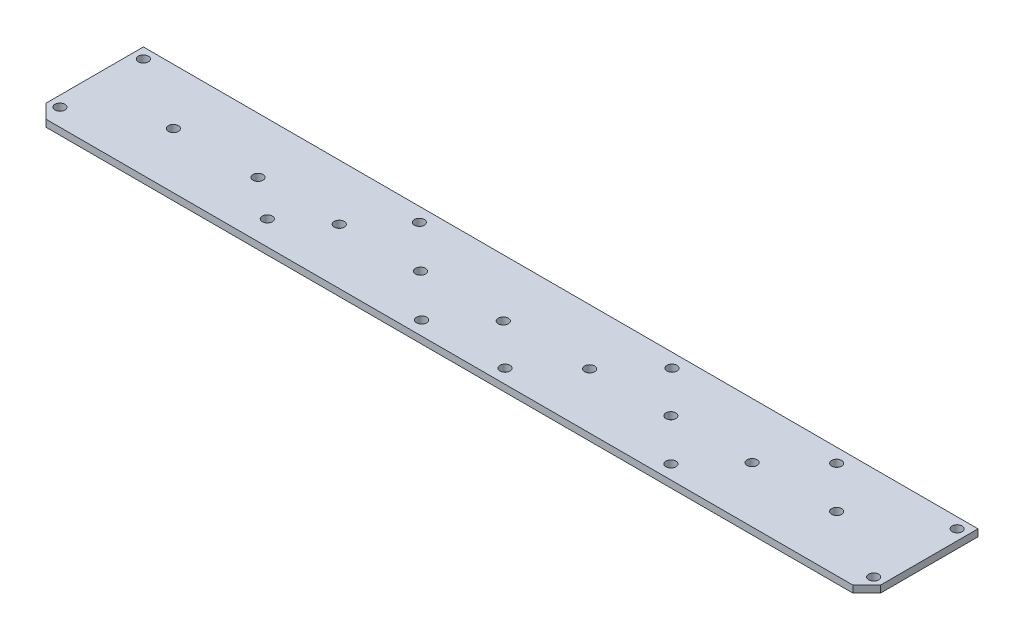
SolidWorks part; units mm, degrees
ref_plane "Front Plane" through (0, 0, 0) normal (0, 0, 1) x (1, 0, 0)
ref_plane "Top Plane" through (0, 0, 0) normal (0, 1, 0) x (1, 0, 0)
ref_plane "Right Plane" through (0, 0, 0) normal (1, 0, 0) x (0, 0, -1)
sketch "Sketch2" plane through (0, 0, 0) normal (0, 1, 0) x (1, 0, 0)
  line L0 (0, 0) -> (0, 50.8)
  line L1 (0, 50.8) -> (381, 50.8)
  line L2 (381, 50.8) -> (381, 0)
  line L3 (381, 0) -> (0, 0)
  dimension "D1" = 50.8
  dimension "D2" = 381
extrude "Boss-Extrude1" add sketch "Sketch2" along normal blind 3.175
sketch "Sketch3" plane through (0, 0, 0) normal (0, 1, 0) x (1, 0, 0)
  line L0 (0, 6.35) -> (6.35, 0) construction
  line L1 (374.65, 0) -> (381, 6.35) construction
  line L2 (0, 6.35) -> (6.35, 0)
  line L3 (374.65, 0) -> (381, 6.35)
  line L4 (0, 6.35) -> (0, 0)
  line L5 (0, 0) -> (6.35, 0)
  line L7 (381, 6.35) -> (381, 0)
  line L8 (381, 0) -> (374.65, 0)
  circle A19 centre (96.266, 11.1125) radius 2.286 construction
  circle A20 centre (285.242, 6.35) radius 2.286 construction
  circle A21 centre (322.834, 44.45) radius 2.286 construction
  circle A22 centre (132.334, 44.45) radius 2.286 construction
  circle A23 centre (247.65, 44.45) radius 2.286 construction
  circle A24 centre (209.55, 6.35) radius 2.286 construction
  circle A25 centre (171.45, 6.35) radius 2.286 construction
  circle A26 centre (4.7625, 7.9375) radius 2.286 construction
  circle A27 centre (4.7625, 46.0375) radius 2.286 construction
  circle A28 centre (39.116, 25.4) radius 2.286 construction
  circle A29 centre (77.724, 25.4) radius 2.286 construction
  circle A30 centre (114.808, 25.4) radius 2.286 construction
  circle A32 centre (190.5, 24.6062) radius 2.286 construction
  circle A36 centre (341.884, 25.4) radius 2.286 construction
  circle A37 centre (376.2375, 7.9375) radius 2.286 construction
  circle A38 centre (376.2375, 46.0375) radius 2.286 construction
  circle A39 centre (96.266, 11.1125) radius 2.286
  circle A40 centre (285.242, 6.35) radius 2.286
  circle A41 centre (322.834, 44.45) radius 2.286
  circle A42 centre (132.334, 44.45) radius 2.286
  circle A43 centre (247.65, 44.45) radius 2.286
  circle A44 centre (209.55, 6.35) radius 2.286
  circle A45 centre (171.45, 6.35) radius 2.286
  circle A46 centre (4.7625, 7.9375) radius 2.286
  circle A47 centre (4.7625, 46.0375) radius 2.286
  circle A48 centre (39.116, 25.4) radius 2.286
  circle A49 centre (77.724, 25.4) radius 2.286
  circle A50 centre (114.808, 25.4) radius 2.286
  circle A52 centre (190.5, 24.6062) radius 2.286
  circle A56 centre (341.884, 25.4) radius 2.286
  circle A57 centre (376.2375, 7.9375) radius 2.286
  circle A58 centre (376.2375, 46.0375) radius 2.286
  circle A59 centre (303.276, 25.4) radius 2.286
  circle A60 centre (266.192, 25.4) radius 2.286
  circle A61 centre (229.108, 25.4) radius 2.286
  circle A62 centre (151.892, 25.4) radius 2.286
  dimension "D1" = 4.572
extrude "Cut-Extrude1" cut sketch "Sketch3" along normal through all
